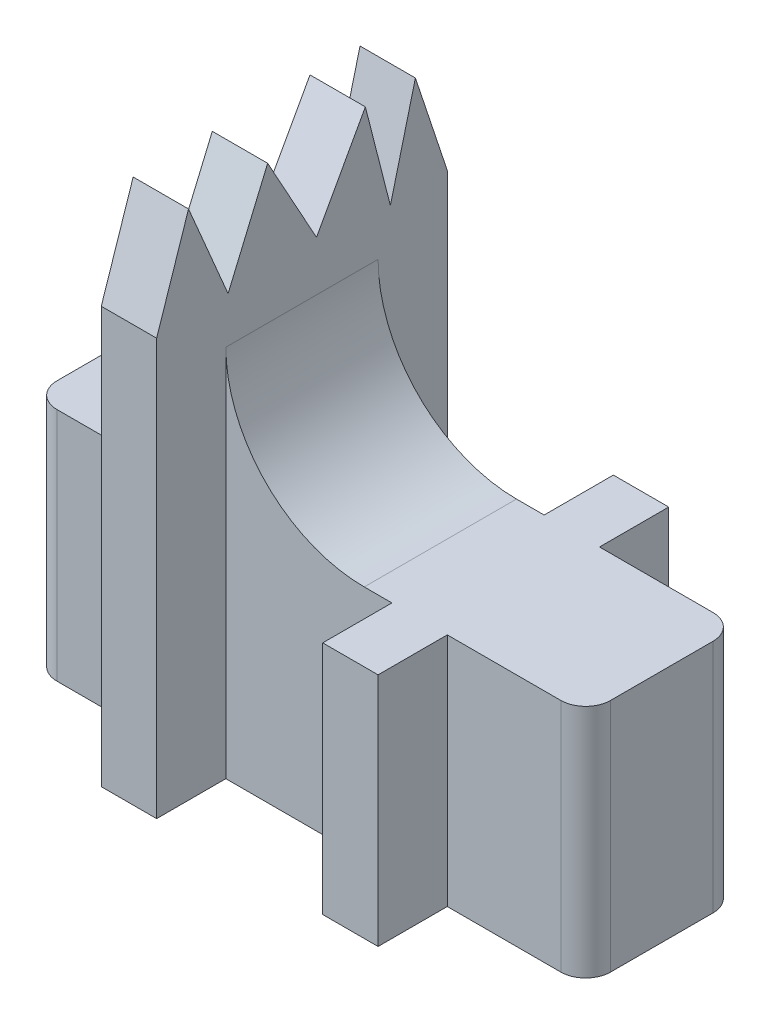
SolidWorks part; units mm, degrees
ref_plane "Front Plane" through (0, 0, 0) normal (0, 0, 1) x (1, 0, 0)
ref_plane "Top Plane" through (0, 0, 0) normal (0, 1, 0) x (1, 0, 0)
ref_plane "Right Plane" through (0, 0, 0) normal (1, 0, 0) x (0, 0, -1)
sketch "Sketch1" plane through (0, 0, 0) normal (0, 1, 0) x (1, 0, 0)
  line L0 (-10, 0) -> (10, 0) construction
  line L1 (-10, -2.75) -> (10, -2.75)
  line L2 (-10, -2.75) -> (-10, 2.75)
  line L3 (-10, 2.75) -> (10, 2.75)
  line L5 (-10, -2.75) -> (0, 0) construction
  line L6 (-10, 2.75) -> (0, 0) construction
  line L7 (0, 2.75) -> (0, -2.75)
  line L8 (-5, -5.25) -> (-3, -5.25)
  line L9 (-5, -5.25) -> (-5, 5.25)
  line L10 (-5, 5.25) -> (-3, 5.25)
  line L11 (-3, -5.25) -> (-3, 5.25)
  line L12 (-5, -5.25) -> (-3, 5.25) construction
  line L13 (-5, 5.25) -> (-3, -5.25) construction
  line L18 (5, 5.25) -> (3, -5.25) construction
  line L19 (5, -5.25) -> (3, 5.25) construction
  line L20 (10, 2.75) -> (0, 0) construction
  line L21 (10, -2.75) -> (0, 0) construction
  line L22 (3, -5.25) -> (3, 5.25)
  line L23 (5, 5.25) -> (3, 5.25)
  line L24 (5, -5.25) -> (5, 5.25)
  line L25 (5, -5.25) -> (3, -5.25)
  line L26 (10, -2.75) -> (10, 2.75)
  point P0 (0, 0)
  point P8 (-4, 0)
  point P22 (4, 0)
  dimension "D1" = 3
  dimension "D2" = 2.5
  dimension "D3" = 5.5
  dimension "D4" = 5
  dimension "D5" = 2
extrude "Boss-Extrude1" add sketch "Sketch1" along normal blind 8.5 contours L1 L9 L3 L2 | L3 L11 L10 L9 | L8 L11 L1 L9 | L1 L11 L3 L9 | L11 L1 L7 L3 | L1 L22 L3 L7 | L3 L24 L23 L22 | L1 L26 L3 L24 | L1 L24 L3 L22 | L25 L24 L1 L22 region at (-7.5, 0, 0) region at (-4, 0, 0) region at (-4, 0, 4) region at (-1.5, 0, 0) region at (-4, 0, -4) region at (1.5, 0, 0) region at (4, 0, 0) region at (4, 0, 4) region at (7.5, 0, 0) region at (4, 0, -4)
fillet "Fillet1" radius 0.9 4 edges at (10, 4.25, -2.75) (10, 4.25, 2.75) (-10, 4.25, 2.75) (-10, 4.25, -2.75)
sketch "Sketch2" plane through (0, 8.5, 0) normal (0, 1, 0) x (1, 0, 0)
  line L1 (-5, 5.25) -> (-3, 5.25)
  line L2 (-5, 5.25) -> (-5, -5.25)
  line L3 (-5, -5.25) -> (-3, -5.25)
  line L4 (-3, 5.25) -> (-3, -5.25)
extrude "Boss-Extrude2" add sketch "Sketch2" along normal blind 10
sketch "Sketch3" plane through (-5, 0, 0) normal (-1, 0, 0) x (0, 0, 1)
  line L0 (-5.25, 15.0317) -> (-4.0979, 18.5)
  line L1 (-5.25, 15.0317) -> (-5.25, 18.5)
  line L2 (-5.25, 18.5) -> (5.25, 18.5)
  line L3 (5.25, 18.5) -> (5.25, 15.0317)
  line L6 (-5.25, 18.5) -> (-5.25, 0) construction
  line L7 (-5.25, 18.5) -> (5.25, 18.5) construction
  line L8 (-4.0979, 18.5) -> (-3.1943, 14.9588)
  line L10 (-3.1943, 14.9588) -> (-2.2907, 18.5)
  line L11 (-2.2907, 18.5) -> (-0.5257, 15.2998)
  line L12 (-0.5257, 15.2998) -> (1.2393, 18.5)
  line L13 (1.2393, 18.5) -> (2.6686, 15.1364)
  line L15 (2.6686, 15.1364) -> (4.0979, 18.5)
  line L16 (4.0979, 18.5) -> (5.25, 15.0317)
  line L17 (5.25, 18.5) -> (5.25, 0) construction
  line M16 (5.25, 0) -> (5.25, 18.5)
  line M17 (5.25, 18.5) -> (-5.25, 18.5)
  line M18 (-5.25, 18.5) -> (-5.25, 0)
extrude "Cut-Extrude1" cut sketch "Sketch3" against normal through all contours L0 M18 M17 | L8 L10 L2 | L11 L12 L2 | L13 L15 L2 | L16 M17 M16 region at (-5, 17.3439, -4.866) region at (-5, 17.3439, 4.866) region at (-5, 17.3788, 2.6686) region at (-5, 17.4333, -0.5257) region at (-5, 17.3196, -3.1943)
fillet "Fillet2" radius 5 1 edges at (-3, 8.5, 0)
